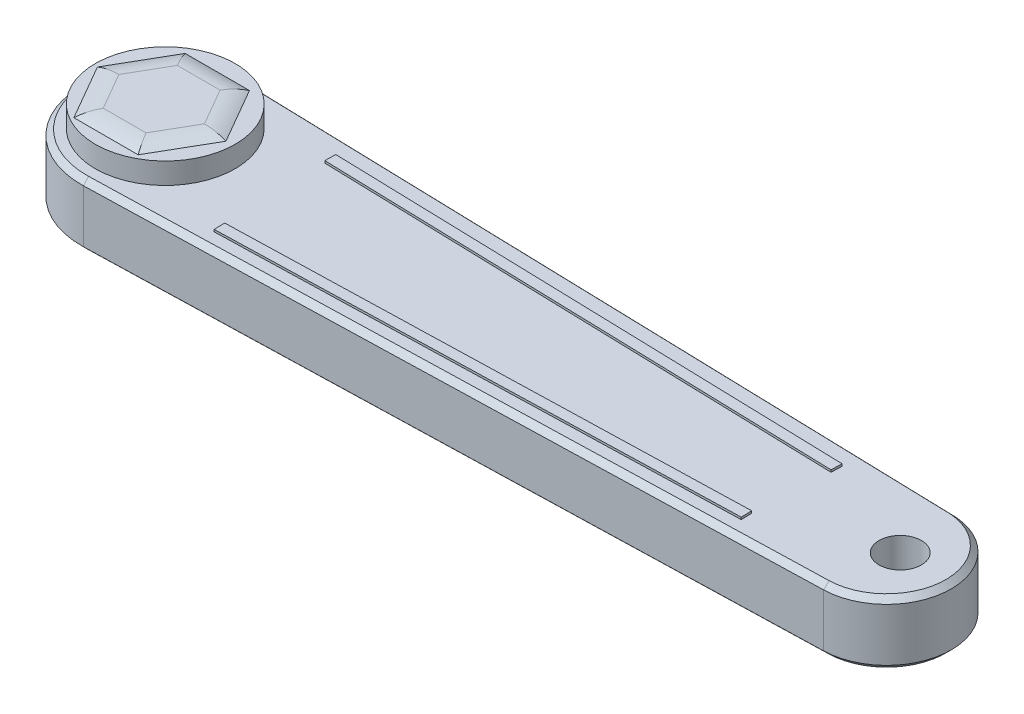
SolidWorks part; units mm, degrees
ref_plane "Front Plane" through (0, 0, 0) normal (0, 0, 1) x (1, 0, 0)
ref_plane "Top Plane" through (0, 0, 0) normal (0, 1, 0) x (1, 0, 0)
ref_plane "Right Plane" through (0, 0, 0) normal (1, 0, 0) x (0, 0, -1)
sketch "Sketch1" plane through (0, 0, 0) normal (0, 1, 0) x (1, 0, 0)
  line L0 (-75.1727, 19.3) -> (93.6924, 14.5493)
  line L1 (-75.1766, -20.6843) -> (94.6908, -15.9383)
  arc A0 (-75.1727, 19.3) -> (-75.1766, -20.6843) centre (-75.7352, -0.6921) ccw
  arc A1 (94.6908, -15.9383) -> (93.6924, 14.5493) centre (94.2648, -0.6921) ccw
  dimension "D1" = 170
extrude "Boss-Extrude2" add sketch "Sketch1" along normal mid plane 15 contours L0 A1 L1 A0
chamfer "Chamfer3" distance 1.27 angle 45 4 edges at (9.2598, 7.5, -16.9247) (109.5088, 7.5, 0.1929) (9.7571, 7.5, 18.3113) (-95.7352, 7.5, 0.6902)
chamfer "Chamfer4" distance 1.27 angle 45 4 edges at (9.7571, -7.5, 18.3113) (109.5088, -7.5, 0.1929) (9.2598, -7.5, -16.9247) (-95.7352, -7.5, 0.6902)
sketch "Sketch2" plane through (0, 7.5, 0) normal (0, 1, 0) x (1, 0, 0)
  circle A0 centre (-75.9727, -0.5801) radius 16.5
sketch "Sketch3" plane through (0, 7.5, 0) normal (0, 1, 0) x (1, 0, 0)
  circle A0 centre (97.369, -0.5801) radius 5
extrude "Boss-Extrude4" add sketch "Sketch2" along normal blind 5 contours A0
extrude "Cut-Extrude1" cut sketch "Sketch3" against normal blind 10 contours A0
sketch "Sketch4" plane through (0, -7.5, 0) normal (0, -1, 0) x (1, 0, 0)
  circle A0 centre (-77.7643, 0) radius 5
extrude "Boss-Extrude5" add sketch "Sketch4" along normal blind 10
sketch "Sketch5" plane through (0, 12.5, 0) normal (0, 1, 0) x (1, 0, 0)
  line L1 (-83.9329, -14.1727) -> (-68.7749, -14.1727)
  line L2 (-68.7749, -14.1727) -> (-61.1958, -1.0455)
  line L3 (-61.1958, -1.0455) -> (-68.7749, 12.0818)
  line L4 (-68.7749, 12.0818) -> (-83.9329, 12.0818)
  line L5 (-83.9329, 12.0818) -> (-91.512, -1.0455)
  line L6 (-91.512, -1.0455) -> (-83.9329, -14.1727)
  circle A0 centre (-76.3539, -1.0455) radius 13.1273 construction
extrude "Boss-Extrude6" add sketch "Sketch5" along normal blind 1.016 contours L4 L5 L6 L1 L2 L3
sketch "Sketch6" plane through (0, 7.5, 0) normal (0, 1, 0) x (1, 0, 0)
  line L0 (-50.0021, 13.6825) -> (72.855, 10.2262)
  line L1 (93.6993, 13.2786) -> (-75.2084, 18.0305) construction
  point P4 (76.659, 10.3366)
  point P5 (72.855, 10.2262)
extrude "Extrude-Thin1" add sketch "Sketch6" along normal blind 0.508 thin contours L0
fillet "Fillet1" radius 10 6 edges at (-64.9854, 13.516, 7.6091) (-76.3539, 13.516, 14.1727) (-87.7225, 13.516, 7.6091) (-87.7225, 13.516, -5.5182) (-76.3539, 13.516, -12.0818) (-64.9854, 13.516, -5.5182)
sketch "Sketch7" plane through (0, 7.5, 0) normal (0, 1, 0) x (1, 0, 0)
  line L0 (-49.1275, -13.4109) -> (71.7925, -10.0324)
  line L2 (-75.2121, -19.4148) -> (94.6553, -14.6688) construction
  point P4 (71.7925, -10.0324)
extrude "Extrude-Thin3" add sketch "Sketch7" along normal blind 0.508 thin contours L0
